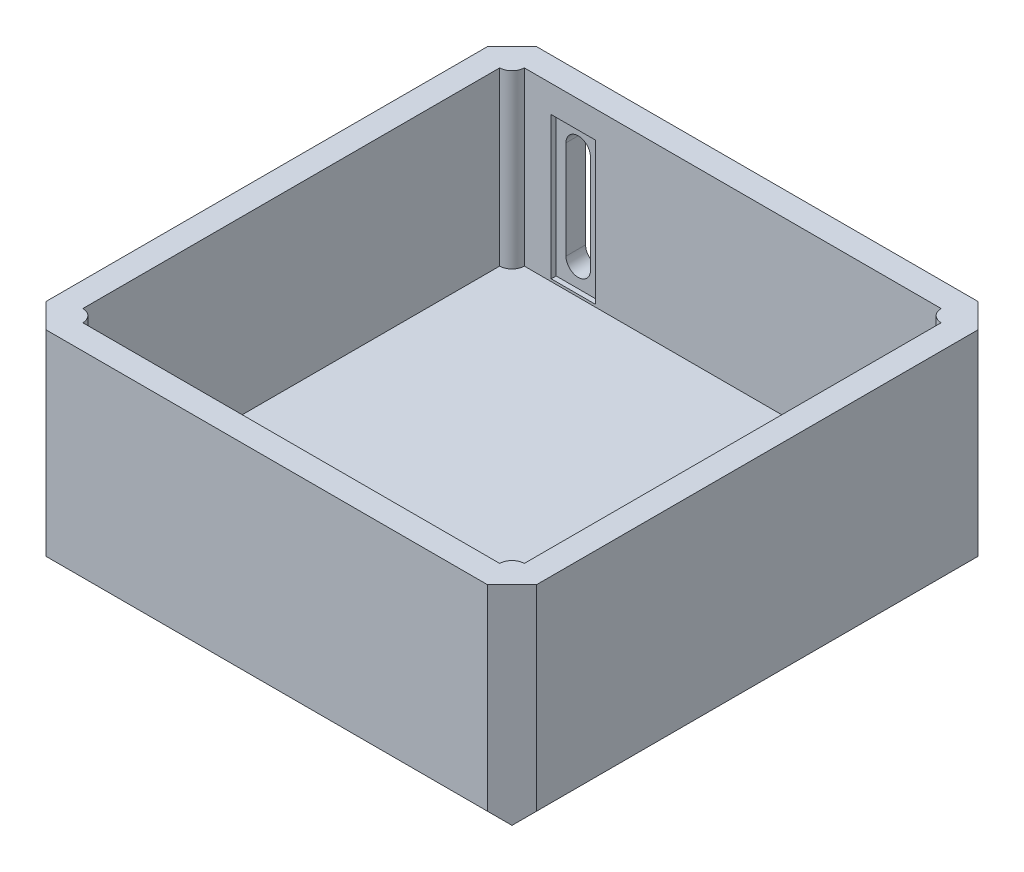
SolidWorks part; units mm, degrees
ref_plane "Front Plane" through (0, 0, 0) normal (0, 0, 1) x (1, 0, 0)
ref_plane "Top Plane" through (0, 0, 0) normal (0, 1, 0) x (1, 0, 0)
ref_plane "Right Plane" through (0, 0, 0) normal (1, 0, 0) x (0, 0, -1)
sketch "Sketch1" plane through (0, 0, 0) normal (0, 1, 0) x (1, 0, 0)
  line L1 (100, -100) -> (-100, -100)
  line L2 (100, -100) -> (100, 100)
  line L3 (100, 100) -> (-100, 100)
  line L4 (-100, -100) -> (-100, 100)
  line L5 (100, -100) -> (-100, 100) construction
  line L6 (100, 100) -> (-100, -100) construction
  point P0 (0, 0)
  dimension "D1" = 200
  dimension "D2" = 200
extrude "Boss-Extrude1" add sketch "Sketch1" along normal blind 100
chamfer "Chamfer1" distance 20 angle 45 4 edges at (100, 0, 0) (0, 0, -100) (-100, 0, 0) (0, 0, 100)
sketch "Sketch2" plane through (0, 100, 0) normal (0, 1, 0) x (1, 0, 0)
  line L0 (0, 0) -> (-179.5549, 0) construction
  line L1 (0, 0) -> (0, 117.1127) construction
  line L2 (-100, 100) -> (-100, -100) construction
  line L3 (100, 100) -> (-100, 100) construction
  line L4 (-84, 90) -> (84, 90)
  line L5 (90, 85) -> (90, -85)
  line L6 (84, -90) -> (-84, -90)
  line L7 (-90, 85) -> (-90, -85)
  line L8 (84, 90) -> (85, 90)
  line L9 (-84, 90) -> (-85, 90)
  line L10 (-84, -90) -> (-85, -90)
  line L11 (84, -90) -> (85, -90)
  circle A0 centre (-90, 90) radius 2
  circle A1 centre (90, 90) radius 2
  circle A2 centre (90, -90) radius 2
  circle A3 centre (-90, -90) radius 2
  circle A4 centre (-90, 90) radius 5
  circle A5 centre (90, 90) radius 5
  circle A6 centre (90, -90) radius 5
  circle A7 centre (-90, -90) radius 5
  dimension "D1" = 4
  dimension "D2" = 10
  dimension "D3" = 10
  dimension "D4" = 3
extrude "Cut-Extrude3" cut sketch "Sketch2" against normal blind 70 contours L7 A7 L6 A6 L5 A5 L4 A4 region at (0, 100, 0)
sketch "Sketch6" plane through (0, 100, 0) normal (0, 1, 0) x (1, 0, 0)
extrude "Cut-Extrude4" cut sketch "Sketch2<7>" against normal through all from offset 70 contours A2 | A3 | A0 | A1 region at (90, 100, 90) offset against normal yes
sketch "Sketch2<7>" plane through (0, 100, 0) normal (0, 1, 0) x (1, 0, 0) same geometry as "Sketch2"
sketch "Sketch7" plane through (0, 0, -100) normal (0, 0, -1) x (-1, 0, 0)
  line L0 (65, 80) -> (65, 40) construction
  line L1 (70, 80) -> (70, 40)
  line L2 (60, 80) -> (60, 40)
  line L3 (100, 100) -> (100, 20) construction
  line L4 (100, 60) -> (60, 60) construction
  arc A0 (70, 80) -> (60, 80) centre (65, 80) ccw
  arc A1 (60, 40) -> (70, 40) centre (65, 40) ccw
  point P2 (65, 60)
  dimension "D2" = 5
  dimension "D3" = 40
  dimension "D1" = 30
extrude "Cut-Extrude7" cut sketch "Sketch7" against normal up to surface (10 mm away) up to face at (0, 65, -90)
sketch "Sketch9" plane through (0, 0, -90) normal (0, 0, 1) x (1, 0, 0)
  line L0 (-60, 60) -> (-56, 60) construction
  line L1 (-74, 89) -> (-56, 89)
  line L2 (-74, 89) -> (-74, 31)
  line L3 (-74, 31) -> (-56, 31)
  line L4 (-56, 89) -> (-56, 31)
  line L5 (-60, 80) -> (-60, 40) construction
  line L6 (-65, 35) -> (-65, 31) construction
  arc A0 (-70, 40) -> (-60, 40) centre (-65, 40) ccw construction
  dimension "D1" = 4
  dimension "D2" = 4
extrude "Cut-Extrude8" cut sketch "Sketch9" against normal blind 2
extrude "Cut-Extrude9" cut sketch "Sketch2<8>" against normal through all from offset 80 contours A5 A1 | A6 A2 | A7 A3 | A4 A0 region at (-86.5645, 100, -86.5645) region at (90, 100, -94.8586) region at (-86.5645, 100, 86.5645) region at (93.4355, 100, 86.5645) offset against normal yes
sketch "Sketch2<8>" plane through (0, 100, 0) normal (0, 1, 0) x (1, 0, 0) same geometry as "Sketch2"
chamfer "Chamfer2" distance 10 angle 45 4 edges at (100, 60, 100) (-100, 60, 100) (-100, 60, -100) (100, 60, -100)
